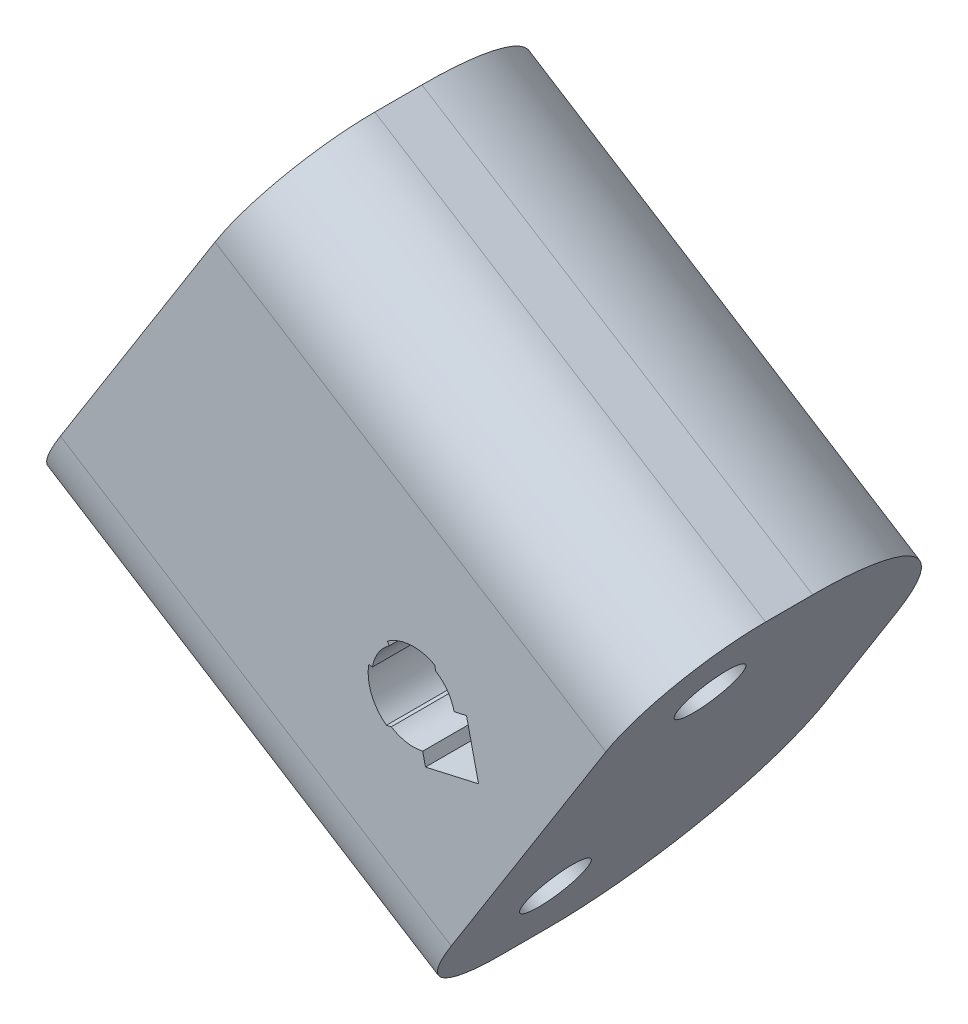
SolidWorks part; units mm, degrees
ref_plane "Front Plane" through (0, 0, 0) normal (0, 0, 1) x (1, 0, 0)
ref_plane "Top Plane" through (0, 0, 0) normal (0, 1, 0) x (1, 0, 0)
ref_plane "Right Plane" through (0, 0, 0) normal (1, 0, 0) x (0, 0, -1)
sketch "Sketch1" plane through (-2.1153, 1.3325, 0) normal (0.8461, -0.533, 0) x (0, 0, -1)
  line L1 (-4.625, 13.75) -> (16.125, 13.75)
  line L2 (-4.625, 13.75) -> (-4.625, -13.75)
  line L3 (-4.625, -13.75) -> (16.125, -13.75)
  line L4 (16.125, 13.75) -> (16.125, -13.75)
  line L9 (16.125, -2.5) -> (16.125, 2.5)
  line L10 (14.125, -2.5) -> (16.125, -2.5)
  line L11 (14.125, 0) -> (14.125, -2.5)
  line L12 (14.125, 2.5) -> (14.125, 0)
  line L13 (16.125, 2.5) -> (14.125, 2.5)
  line L14 (16.125, -2.5) -> (16.125, 2.5)
  line L15 (14.125, -2.5) -> (16.125, -2.5)
  line L16 (14.125, 0) -> (14.125, -2.5)
  line L17 (14.125, 2.5) -> (14.125, 0)
  line L18 (16.125, 2.5) -> (14.125, 2.5)
  circle A0 centre (1.125, 8) radius 5.75
  circle A1 centre (-87.3, 43.2576) radius 1.525
  circle A2 centre (-87.3, 43.2576) radius 1.525
  circle A3 centre (-40.2892, -43.1701) radius 1.525
  circle A4 centre (-40.2892, -43.1701) radius 1.525
  circle A5 centre (-87.1389, -43.3445) radius 1.525
  circle A6 centre (-87.1389, -43.3445) radius 1.525
  circle A7 centre (-40.45, 43.2576) radius 1.525
  circle A8 centre (-40.45, 43.2576) radius 1.525
  circle A9 centre (-30.875, 40) radius 1.75
  circle A10 centre (-30.875, 40) radius 1.75
  circle A11 centre (-96.875, -20) radius 1.75
  circle A12 centre (-96.875, -20) radius 1.75
  circle A13 centre (-96.875, 0) radius 1.75
  circle A14 centre (-96.875, 0) radius 1.75
  circle A15 centre (-20.875, 0) radius 1.75
  circle A16 centre (-20.875, 0) radius 1.75
  circle A17 centre (-94.875, 45) radius 1.75
  circle A18 centre (-94.875, 45) radius 1.75
  circle A19 centre (-20.875, 20) radius 1.75
  circle A20 centre (-20.875, 20) radius 1.75
  circle A21 centre (-96.875, 20) radius 1.75
  circle A22 centre (-96.875, 20) radius 1.75
  circle A23 centre (-22.1557, -52.2046) radius 1.75
  circle A24 centre (-22.1557, -52.2046) radius 1.75
  circle A25 centre (-13.1629, 43.1009) radius 1.75
  circle A26 centre (-13.1629, 43.1009) radius 1.75
  circle A27 centre (-22.1557, 52.2046) radius 1.75
  circle A28 centre (-22.1557, 52.2046) radius 1.75
  circle A29 centre (-13.1629, -43.1009) radius 1.75
  circle A30 centre (-13.1629, -43.1009) radius 1.75
  circle A31 centre (-6.1189, -32.4177) radius 1.75
  circle A32 centre (-6.1189, -32.4177) radius 1.75
  circle A33 centre (-1.2945, -20.5656) radius 1.75
  circle A34 centre (-1.2945, -20.5656) radius 1.75
  circle A35 centre (1.125, -8) radius 1.75
  circle A36 centre (1.125, -8) radius 1.75
  circle A37 centre (1.125, 8) radius 1.75
  circle A38 centre (1.125, 8) radius 1.75
  circle A39 centre (-1.2945, 20.5656) radius 1.75
  circle A40 centre (-1.2945, 20.5656) radius 1.75
  circle A41 centre (-6.1189, 32.4177) radius 1.75
  circle A42 centre (-6.1189, 32.4177) radius 1.75
  circle A43 centre (-20.875, -20) radius 1.75
  circle A44 centre (-20.875, -20) radius 1.75
  circle A45 centre (-106.875, -20) radius 1.75
  circle A46 centre (-106.875, -20) radius 1.75
  circle A47 centre (-106.875, 0) radius 1.75
  circle A48 centre (-106.875, 0) radius 1.75
  circle A49 centre (-106.875, 20) radius 1.75
  circle A50 centre (-106.875, 20) radius 1.75
  circle A51 centre (-116.875, 24.5) radius 1.75
  circle A52 centre (-116.875, 24.5) radius 1.75
  circle A53 centre (-30.875, 20) radius 1.75
  circle A54 centre (-30.875, 20) radius 1.75
  circle A55 centre (-94.875, -52) radius 1.75
  circle A56 centre (-94.875, -52) radius 1.75
  circle A57 centre (-30.875, -20) radius 1.75
  circle A58 centre (-30.875, -20) radius 1.75
  circle A59 centre (-30.875, 0) radius 1.75
  circle A60 centre (-30.875, 0) radius 1.75
  circle A61 centre (-116.875, -24.5) radius 1.75
  circle A62 centre (-116.875, -24.5) radius 1.75
  circle A63 centre (-94.875, -45) radius 1.75
  circle A64 centre (-94.875, -45) radius 1.75
  circle A65 centre (-30.875, -40) radius 1.75
  circle A66 centre (-30.875, -40) radius 1.75
  circle A67 centre (-94.875, 52) radius 1.75
  circle A68 centre (-94.875, 52) radius 1.75
  circle A69 centre (-20.875, 40) radius 1.75
  circle A70 centre (-20.875, 40) radius 1.75
  circle A71 centre (-20.875, -40) radius 1.75
  circle A72 centre (-20.875, -40) radius 1.75
  circle A73 centre (-106.875, -40) radius 1.75
  circle A74 centre (-106.875, -40) radius 1.75
  circle A75 centre (-75.875, 15) radius 1
  circle A76 centre (-75.875, 15) radius 1
  circle A77 centre (-106.875, 40) radius 1.75
  circle A78 centre (-106.875, 40) radius 1.75
  circle A79 centre (-51.875, 15) radius 1
  circle A80 centre (-51.875, 15) radius 1
  circle A81 centre (-51.875, -25) radius 1
  circle A82 centre (-51.875, -25) radius 1
  circle A83 centre (-75.875, -25) radius 1
  circle A84 centre (-75.875, -25) radius 1
  circle A85 centre (1.125, -8) radius 5.75
  dimension "D1" = 0
  dimension "D2" = 0
  dimension "D3" = 0
  dimension "D4" = 0
  dimension "D5" = 0
  dimension "D6" = 0
  dimension "D7" = 0
  dimension "D8" = 0
  dimension "D9" = 0
  dimension "D10" = 0
  dimension "D11" = 0
  dimension "D12" = 0
  dimension "D13" = 0
  dimension "D14" = 0
  dimension "D15" = 0
  dimension "D16" = 0
  dimension "D17" = 0
  dimension "D18" = 0
  dimension "D19" = 0
  dimension "D20" = 0
  dimension "D21" = 0
  dimension "D22" = 0
  dimension "D23" = 0
  dimension "D24" = 0
  dimension "D25" = 0
  dimension "D26" = 0
  dimension "D27" = 0
  dimension "D28" = 0
  dimension "D29" = 0
  dimension "D30" = 0
  dimension "D31" = 0
  dimension "D32" = 0
  dimension "D33" = 0
  dimension "D34" = 0
  dimension "D35" = 0
  dimension "D36" = 0
  dimension "D37" = 0
  dimension "D38" = 0
  dimension "D39" = 0
  dimension "D40" = 0
  dimension "D41" = 0
  dimension "D42" = 0
  dimension "D43" = 4
  dimension "D44" = 0
extrude "Boss-Extrude1" add sketch "Sketch1" along normal up to surface (15.4783 mm away) region at (-2.1153, 1.3325, -8.6908) region at (4.2548, 11.4442, -5.0759) region at (-3.4012, -0.7088, -1.125)
sketch "Sketch2" plane through (10.981, -6.9177, 0) normal (0.8461, -0.533, 0) x (0, 0, -1)
  line L0 (16.125, 2.5) -> (14.125, 2.5) construction
  line L1 (14.125, 2.5) -> (14.125, 0) construction
  line L2 (14.125, 0) -> (14.125, -2.5) construction
  line L3 (14.125, -2.5) -> (16.125, -2.5) construction
  line L4 (1.125, -13.75) -> (16.125, -13.75)
  line L5 (16.125, -13.75) -> (16.125, 13.75)
  line L6 (16.125, 13.75) -> (1.125, 13.75)
  line L7 (-4.625, 8) -> (-4.625, -8)
  line L8 (1.125, -13.75) -> (16.125, -13.75)
  line L9 (16.125, -13.75) -> (16.125, 13.75)
  line L10 (16.125, 13.75) -> (1.125, 13.75)
  line L11 (-4.625, 8) -> (-4.625, -8)
  line L12 (16.125, -2.5) -> (16.125, 2.5) construction
  line L13 (16.125, 2.5) -> (14.125, 2.5) construction
  line L14 (14.125, 2.5) -> (14.125, 0)
  line L15 (14.125, 0) -> (14.125, -2.5)
  line L16 (14.125, -2.5) -> (16.125, -2.5)
  line L17 (16.125, -2.5) -> (16.125, 2.5)
  line L18 (16.525, 2.9) -> (13.725, 2.9)
  line L19 (13.725, 2.9) -> (13.725, 0)
  line L20 (13.725, 0) -> (13.725, -2.9)
  line L21 (13.725, -2.9) -> (16.525, -2.9)
  line L22 (16.525, -2.9) -> (16.525, 2.9)
  line L23 (13.725, 2.9) -> (13.725, 13.75)
  line L24 (13.725, -2.9) -> (13.725, -13.75)
  circle A1 centre (1.125, -8) radius 1.75
  arc A2 (1.125, 13.75) -> (-4.625, 8) centre (1.125, 8) ccw
  arc A3 (-4.625, -8) -> (1.125, -13.75) centre (1.125, -8) ccw
  arc A4 (1.125, 13.75) -> (-4.625, 8) centre (1.125, 8) ccw
  arc A5 (-4.625, -8) -> (1.125, -13.75) centre (1.125, -8) ccw
  circle A6 centre (1.125, -8) radius 1.75
  circle A7 centre (1.125, 8) radius 1.75
  circle A8 centre (1.125, 8) radius 1.75
  line M15 (1.125, -13.75) -> (16.125, -13.75)
  line M16 (16.125, -13.75) -> (16.125, 13.75)
  line M17 (16.125, 13.75) -> (1.125, 13.75)
  arc M18 (1.125, 13.75) -> (-4.625, 8) centre (1.125, 8) ccw
  line M19 (-4.625, 8) -> (-4.625, -8)
  arc M20 (-4.625, -8) -> (1.125, -13.75) centre (1.125, -8) ccw
  circle M21 centre (1.125, -8) radius 1.75
  circle M22 centre (1.125, 8) radius 1.75
  dimension "D1" = 0
  dimension "D2" = 0
  dimension "D3" = 0
  dimension "D4" = 0.4
extrude "Boss-Extrude2" add sketch "Sketch2" along normal blind 10 contours L21 L20 L19 L18 L9 M17 M18 M19 M20 M15 M16 M21 M22 region at (10.981, -6.9177, -4.9275)
sketch "Sketch3" plane through (0, 0, -13.725) normal (0, 0, -1) x (-1, 0, 0)
  line L4 (-3.652, -18.5516) -> (-18.31, 4.7163)
  line L5 (-18.31, 4.7163) -> (-26.771, -0.6139)
  line L6 (-26.771, -0.6139) -> (-12.1131, -23.8818)
  line L8 (-3.652, -18.5516) -> (-18.31, 4.7163)
  line L10 (-26.771, -0.6139) -> (-12.1131, -23.8818)
  line L18 (-18.31, 4.7163) -> (-26.771, -0.6139)
  line L20 (-12.1131, -23.8818) -> (-3.652, -18.5516)
  line L21 (-12.1131, -23.8818) -> (-3.652, -18.5516)
  dimension "D1" = 0
sketch "Sketch5" plane through (10.981, -6.9177, 0) normal (0.8461, -0.533, 0) x (0, 0, -1)
  line L4 (13.725, 13.75) -> (13.725, -13.75)
  line L16 (13.725, 13.75) -> (13.725, -13.75)
  line L20 (13.725, -13.75) -> (16.125, -13.75)
  line L22 (13.725, -13.75) -> (16.125, -13.75)
  line L24 (16.125, -13.75) -> (16.125, 13.75)
  line L25 (16.125, -13.75) -> (16.125, 13.75)
  line L26 (16.125, 13.75) -> (13.725, 13.75)
  line L27 (16.125, 13.75) -> (13.725, 13.75)
  dimension "D1" = 0
extrude "Cut-Extrude1" cut sketch "Sketch5" against normal up to surface (15.4783 mm away) contours L16 L22 L25 L27 up to face at (-2.1153, 1.3325, -3.8114)
sketch "Sketch7" plane through (0, 0, -13.725) normal (0, 0, -1) x (-1, 0, 0)
  line L0 (-13.0963, -8.2502) -> (-19.442, -12.2478) construction
  line L1 (-16.0877, -10.1347) -> (-13.6497, -10.6882) construction
  line L2 (-16.0877, -10.1347) -> (-15.5342, -7.6967) construction
  line L3 (-16.686, -10.5116) -> (-13.7604, -11.1758)
  line L4 (-12.1131, -23.8818) -> (9.4442, -10.3014)
  line L7 (-26.771, -0.6139) -> (-12.1131, -23.8818)
  line L11 (-26.771, -0.6139) -> (-12.1131, -23.8818)
  line L12 (-16.686, -10.5116) -> (-16.0218, -7.586)
  line L13 (-13.0963, -8.2502) -> (-13.7604, -11.1758)
  line L14 (-13.0963, -8.2502) -> (-16.0218, -7.586)
  line L15 (-13.0963, -8.2502) -> (-11.4972, -10.7885)
  line L16 (-11.4972, -10.7885) -> (-13.0963, -8.2502)
  line L17 (-13.0963, -8.2502) -> (-14.6953, -5.7119)
  line L18 (-13.0963, -8.2502) -> (-10.558, -6.6512) construction
  line L19 (-13.0963, -8.2502) -> (-10.1392, -7.7442)
  line L20 (-13.0963, -8.2502) -> (-11.3631, -5.8015)
  line L29 (-12.1131, -23.8818) -> (9.4442, -10.3014)
  line L32 (9.4442, -10.3014) -> (-5.2137, 12.9665)
  line L34 (9.4442, -10.3014) -> (-5.2137, 12.9665)
  line L35 (-5.2137, 12.9665) -> (-26.771, -0.6139)
  line L36 (-5.2137, 12.9665) -> (-26.771, -0.6139)
  circle A0 centre (-13.0963, -8.2502) radius 3
  circle A1 centre (-13.0963, -8.2502) radius 2.5
  circle A2 centre (-13.0963, -8.2502) radius 2.5
  circle A3 centre (-13.0963, -8.2502) radius 2.3
  dimension "D3" = 45
  dimension "D5" = 45
  dimension "D6" = 45
  dimension "D7" = 45
  dimension "D8" = 22.5
  dimension "D9" = 22.5
  dimension "D1" = 0
  dimension "D2" = 0
  dimension "D4" = 0.5
  dimension "D10" = 0.2
extrude "Cut-Extrude2" cut sketch "Sketch7" against normal up to surface (18.35 mm away) contours A0 L12 L3 | A2 L14 A0 L13 | A3 L14 A2 L13 | L14 A3 L13 | L13 A3 L15 | L17 A3 L14 | L15 A3 L19 | A3 L16 A2 L19 | L20 A3 L17 | A3 L20 A2 L17 | L19 A3 L20 region at (15.8842, -10.0065, -13.725) region at (15.5978, -9.8261, -13.725) region at (15.1811, -9.5636, -13.725) region at (14.2643, -8.986, -13.725) region at (12.8443, -9.723, -13.725) region at (11.793, -10.2657, -13.725) region at (14.3159, -7.387, -13.725) region at (13.0298, -5.7796, -13.725) region at (11.7755, -8.8394, -13.725) region at (11.832, -7.4538, -13.725) region at (13.0574, -6.8045, -13.725) up to face at (8.6634, -5.4576, 4.625)
fillet "Fillet1" radius 10 2 edges at (15.9924, 6.1763, -13.725) (1.3344, -17.0916, -13.725)
chamfer "Chamfer1" distance 0.2 angle 45 2 edges at (14.4288, -6.1349, -4.55) (11.7637, -10.3655, -4.55)
equation "\"D8@Sketch7\"=45/2"
equation "\"D9@Sketch7\"=45/2"
